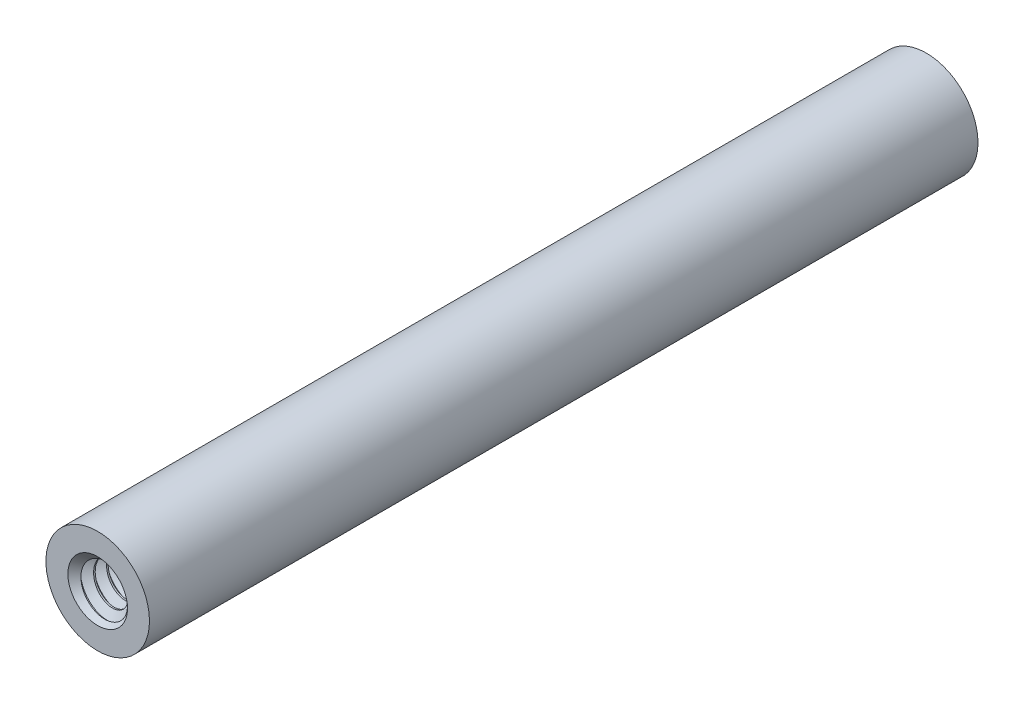
SolidWorks part; units mm, degrees
ref_plane "Front Plane" through (0, 0, 0) normal (0, 0, 1) x (1, 0, 0)
ref_plane "Top Plane" through (0, 0, 0) normal (0, 1, 0) x (1, 0, 0)
ref_plane "Right Plane" through (0, 0, 0) normal (1, 0, 0) x (0, 0, -1)
sketch "Sketch3" plane through (0, 0, 0) normal (1, 0, 0) x (0, 0, -1)
  line L0 (-25.4, 0) -> (25.4, 0) construction
  line L1 (0, 3.175) -> (0, -3.175) construction
  line L2 (-25.4, 1.7526) -> (-25.4, -1.7526) construction
  point P2 (15.875, 0)
  point P3 (-15.875, 0)
  dimension "Length" = 50.8
  dimension "Min Thread Length" = 9.525
  dimension "D1" = 9.525
  dimension "Thread Dia" = 3.5052
  dimension "OD" = 6.35
ref_axis "Axis1" through (0, 3.175, 0) along (0, -1, 0)
sketch "Sketch10" plane through (0, 0, 0) normal (1, 0, 0) x (0, 0, -1)
  line L0 (25.4, 1.7526) -> (15.875, 1.7526)
  line L1 (-25.4, 1.7526) -> (-15.875, 1.7526)
  line L2 (15.875, 1.7526) -> (15.875, -1.7526)
  line L3 (-25.4, -1.7526) -> (-15.875, -1.7526)
  line L4 (-15.875, 1.7526) -> (-15.875, -1.7526)
  line L5 (15.875, -1.7526) -> (25.4, -1.7526)
sketch "Sketch13" plane through (0, 0, 0) normal (0, 0, 1) x (1, 0, 0)
  circle A0 centre (0, 0) radius 1.7526
extrude "Boss-Extrude1" add sketch "Sketch13" against normal up to vertex (-15.875 mm away) from vertex at 25.4 starting at point (0, 0, 25.4)
sketch "Sketch14" plane through (0, 0, 25.4) normal (0, 0, 1) x (1, 0, 0)
  circle A1 centre (0, 0) radius 1.7526
  circle A2 centre (0, 0) radius 1.7526
  dimension "D1" = 0
curve "Helix/Spiral2" pitch 0.7937 height 10.3188 turns 13 parameters "Pitch"=0.7937
sketch "Sketch15" plane through (0, 0, 0) normal (1, 0, 0) x (0, 0, -1)
  line L0 (-26.0945, 1.7526) -> (-25.4, 1.7526)
  line L1 (-26.0945, 1.7526) -> (-25.7969, 1.237)
  line L2 (-25.7969, 1.237) -> (-25.6977, 1.237)
  line L3 (-25.6977, 1.237) -> (-25.4, 1.7526)
  line L4 (-25.7473, 1.237) -> (-25.7473, 1.7526) construction
  line L5 (-25.9457, 1.4948) -> (-25.5488, 1.4948) construction
  dimension "D1" = 60
  dimension "D2" = 0.0992
  dimension "D3" = 0.3969
sweep "Cut-Sweep1" cut profiles "Sketch15" path "Helix/Spiral2" align with end faces yes
sketch "Sketch16" plane through (0, 0, 25.4) normal (0, 0, 1) x (1, 0, 0)
  circle A2 centre (0, 0) radius 1.8288
  circle A3 centre (0, 0) radius 1.8288
  dimension "D1" = 0.0762
extrude "Boss-Extrude2" add sketch "Sketch16" against normal through all draft 45
pattern_circular "CirPattern1" count 2 over 180 about axis through (0, 3.175, 0) along (0, -1, 0) of bodies 113
sketch "Sketch1" plane through (0, 0, 0) normal (0, 0, 1) x (1, 0, 0)
  circle A1 centre (0, 0) radius 1.7526 construction
  circle A2 centre (0, 0) radius 3.175
extrude "Extrude1" add sketch "Sketch1" along normal up to vertex (25.4 mm away) and the other way up to vertex (25.4 mm away) up to point (0, 0, 25.4) other way up to point (0, 0, -25.4)
combine bodies "Combine1" operation type subtract main body 101 bodies to subtract 114 113
equation "\"D1@Sketch3\" = \"Min Thread Length@Sketch3\""
equation "\"D3@Helix/Spiral2\" = \"Min Thread Length@Sketch3\"+\"Pitch@Helix/Spiral2\""
equation "\"D2@Sketch15\" = \"Pitch@Helix/Spiral2\"*.125"
equation "\"D3@Sketch15\" = \"Pitch@Helix/Spiral2\"*.5"
